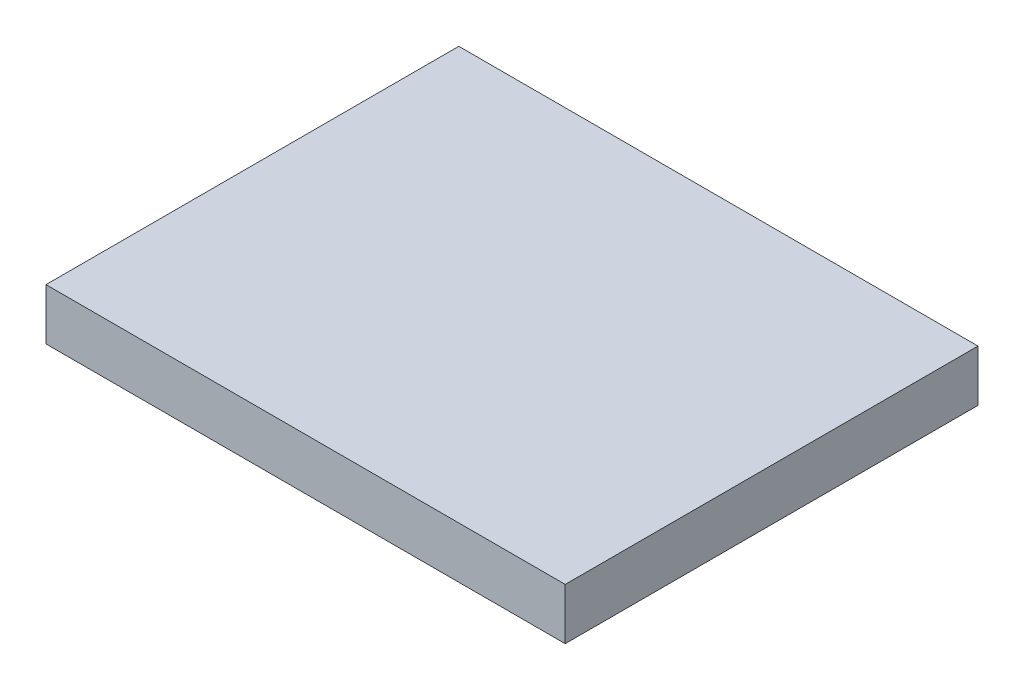
SolidWorks part; units mm, degrees
ref_plane "Front Plane" through (0, 0, 0) normal (0, 0, 1) x (1, 0, 0)
ref_plane "Top Plane" through (0, 0, 0) normal (0, 1, 0) x (1, 0, 0)
ref_plane "Right Plane" through (0, 0, 0) normal (1, 0, 0) x (0, 0, -1)
sketch "Sketch1" plane through (0, 0, 0) normal (0, 1, 0) x (1, 0, 0)
  line L1 (0, 0) -> (283, 0)
  line L2 (0, 0) -> (0, 225)
  line L3 (0, 225) -> (283, 225)
  line L4 (283, 0) -> (283, 225)
  dimension "D1" = 225
  dimension "D2" = 283
extrude "Boss-Extrude1" add sketch "Sketch1" along normal blind 28
equation "\"Length\"= 283"
equation "\"Width\"= 225"
equation "\"WallThickness\"= 12.5"
equation "\"D1@Sketch1\"=\"Width\""
equation "\"D2@Sketch1\"=\"Length\""
equation "\"UpperWaterJacketThickness\"= 28"
equation "\"D1@Boss-Extrude1\"=\"UpperWaterJacketThickness\""
